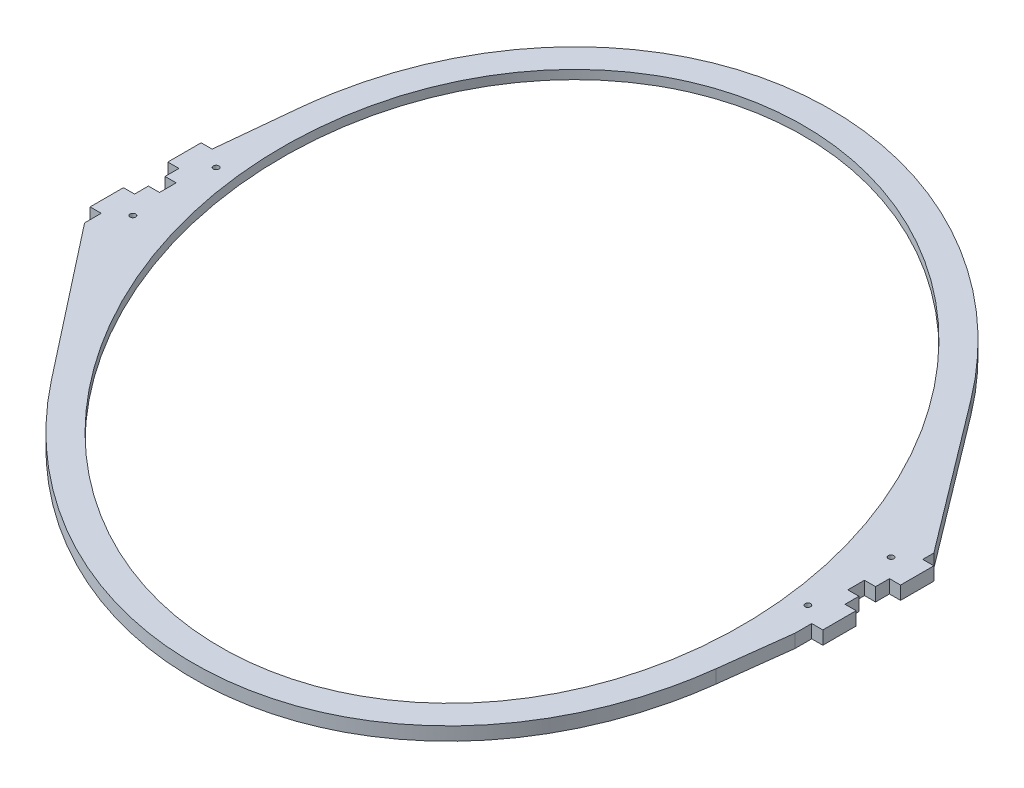
SolidWorks part; units mm, degrees
ref_plane "Front Plane" through (0, 0, 0) normal (0, 0, 1) x (1, 0, 0)
ref_plane "Top Plane" through (0, 0, 0) normal (0, 1, 0) x (1, 0, 0)
ref_plane "Right Plane" through (0, 0, 0) normal (1, 0, 0) x (0, 0, -1)
sketch "Sketch1" plane through (0, 0, 0) normal (0, 1, 0) x (1, 0, 0)
  line L0 (0, 520.2694) -> (0, -520.3963) construction
  line L1 (-478.2136, 0) -> (435.079, 0) construction
  line L2 (-270, 0) -> (-270, 60) construction
  line L3 (-270, 60) -> (-290, 60) construction
  line L4 (-290, 60) -> (-290, -60) construction
  line L5 (-320, 50) -> (-320, 51)
  line L6 (-330, -20) -> (-330, -50)
  line L7 (-320, -50) -> (-320, -65)
  line L8 (-330, -50) -> (-320, -50)
  line L9 (290, 60) -> (290, -60) construction
  line L10 (-320, -20) -> (-330, -20)
  line L11 (-320, 0) -> (-320, -20)
  line L12 (-320, 0) -> (-320, 20)
  line L13 (-320, 20) -> (-330, 20)
  line L14 (-330, 20) -> (-330, 50)
  line L15 (-330, 50) -> (-320, 50)
  line L16 (-320, 51) -> (-313.0913, 120.0927)
  line L17 (-320, -65) -> (-212.2821, -202.5885)
  line L19 (-290, 60) -> (-290, -60) construction
  line L29 (-177.5, 307.439) -> (177.5, -307.439) construction
  line L30 (320, 0) -> (320, 20)
  line L31 (320, 20) -> (330, 20)
  line L32 (330, 20) -> (330, 50)
  line L33 (330, 50) -> (320, 50)
  line L34 (320, 50) -> (320, 60)
  line L35 (320, 0) -> (320, -20)
  line L36 (320, -20) -> (330, -20)
  line L37 (330, -20) -> (330, -50)
  line L38 (330, -50) -> (320, -50)
  line L39 (320, -50) -> (320, -65)
  line L40 (320, -65) -> (312.1702, -128.3352)
  line L41 (320, 60) -> (217.5479, 195.7385)
  ellipse E0 centre (0, 0) end of major axis (-190, 329.0897) minor radius 290 (217.5479, 195.7385) -> (-313.0913, 120.0927) ccw
  ellipse E1 centre (0, 0) end of major axis (0, 380) minor radius 290 construction
  ellipse E3 centre (0, 0) end of major axis (-177.5, 307.439) minor radius 265
  ellipse E7 centre (0, 0) end of major axis (-190, 329.0897) minor radius 290 (-212.2821, -202.5885) -> (312.1702, -128.3352) ccw
  point P27 (290, 0)
  point P32 (-290, 0)
  point P42 (290, 0)
  dimension "D2" = 10
  dimension "D3" = 580
  dimension "D4" = 760
  dimension "D5" = 20
  dimension "D6" = 10
  dimension "D7" = 60
  dimension "D8" = 10
  dimension "D9" = 320
  dimension "D10" = 30
  dimension "D11" = 710
  dimension "D12" = 530
  dimension "D13" = 760
  dimension "D14" = 580
  dimension "D15" = 30
  dimension "D16" = 30
  dimension "D17" = 20
  dimension "D18" = 20
  dimension "D19" = 15
  dimension "D20" = 10
  dimension "D21" = 1
extrude "Boss-Extrude1" add sketch "Sketch1" along normal blind 12
sketch "Sketch2" plane through (0, 12, 0) normal (0, 1, 0) x (1, 0, 0)
  line L0 (0, 0) -> (451.8605, 0) construction
  line L1 (320, -20) -> (320, 20) construction
  line L2 (320, -7.5) -> (310, -7.5)
  line L3 (320, -7.5) -> (320, 7.5)
  line L4 (320, 7.5) -> (310, 7.5)
  line L5 (310, -7.5) -> (310, 7.5)
  line L6 (0, 0) -> (0, 314.2562) construction
  line L7 (-310, -7.5) -> (-310, 7.5)
  line L8 (-320, 7.5) -> (-310, 7.5)
  line L9 (-320, -7.5) -> (-320, 7.5)
  line L10 (-320, -7.5) -> (-310, -7.5)
  point P3 (-320, 0)
  point P10 (310, 0)
  point P11 (320, 0)
  point P13 (-310, 0)
  dimension "D1" = 15
  dimension "D2" = 10
extrude "Cut-Extrude1" cut sketch "Sketch2" against normal blind 12
hole_wizard "Ø5.0 (5) Diameter Hole2" positions "Sketch5" profile "Sketch6" hole size "Ø5.0" standard "ANSI Metric"
sketch "Sketch5" plane through (0, 12, 0) normal (0, 1, 0) x (1, 0, 0)
  point P0 (304, 37.5)
  point P3 (304, -37.5)
  point P6 (-304, -37.5)
  point P9 (-304, 37.5)
sketch "Sketch6" plane through (304, 12, -37.5) normal (1, 0, 0) x (0, 0, 1)
  line L0 (0, 0) -> (0, 26.5022)
  line L1 (0, 26.5022) -> (2.5, 25)
  line L2 (2.5, 25) -> (2.5, 0)
  line L3 (2.5, 0) -> (0, 0)
  line L4 (0, 26.5022) -> (-2.5, 25) construction
  line L5 (0, -6.35) -> (0, 107.95) construction
  dimension "Hole Dia." = 5
  dimension "Hole Depth" = 25
  dimension "Drill Angle" = 118
sketch "Sketch9" plane through (0, 0, 0) normal (0, -1, 0) x (1, 0, 0)
  line L0 (0, 0) -> (177.5, 307.439) construction
  line L1 (0, 0) -> (229.4967, -132.5) construction
  ellipse E0 centre (0, 0) end of major axis (182.5, 316.0993) minor radius 275
  ellipse E1 centre (0, 0) end of major axis (-177.5, -307.439) minor radius 265 construction
  dimension "D1" = 10
  dimension "D2" = 10
extrude "Cut-Extrude4" cut sketch "Sketch9" against normal blind 4
sketch "Sketch7" plane through (0, 12, 0) normal (0, 1, 0) x (1, 0, 0)
  line L0 (0, 0) -> (-211.3091, 453.1539)
  line L1 (0, 0) -> (211.3091, -453.1539)
  line L2 (0, 0) -> (0, 490.0448) construction
  arc A0 (-211.3091, 453.1539) -> (211.3091, -453.1539) centre (0, 0) ccw
  dimension "D2" = 500
  dimension "D1" = 25
extrude "Cut-Extrude2" [suppressed] cut sketch "Sketch7" against normal blind 12
sketch "Sketch8" plane through (0, 12, 0) normal (0, 1, 0) x (1, 0, 0)
  line L0 (0, 0) -> (-211.3091, 453.1539)
  line L1 (0, 0) -> (211.3091, -453.1539)
  line L2 (0, 0) -> (0, 207.06) construction
  arc A0 (-211.3091, 453.1539) -> (211.3091, -453.1539) centre (0, 0) cw
  dimension "D2" = 500
  dimension "D1" = 25
extrude "Cut-Extrude3" [suppressed] cut sketch "Sketch8" against normal blind 12
